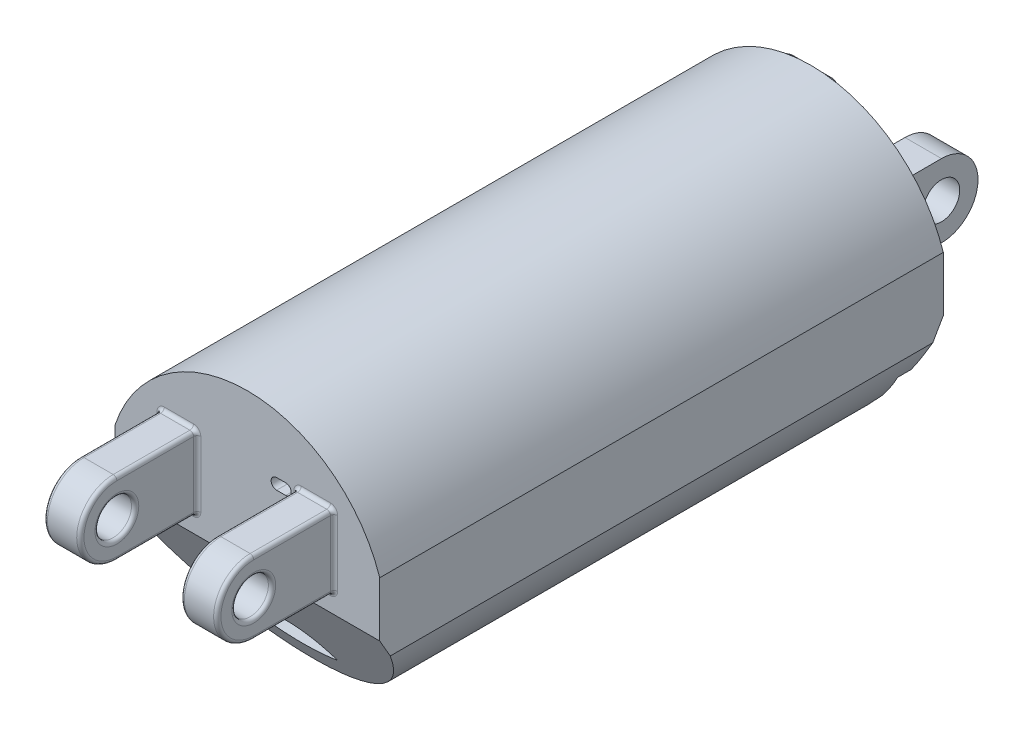
SolidWorks part; units mm, degrees
material "PET"
ref_plane "Front Plane" through (0, 0, 0) normal (0, 0, 1) x (1, 0, 0)
ref_plane "Top Plane" through (0, 0, 0) normal (0, 1, 0) x (1, 0, 0)
ref_plane "Right Plane" through (0, 0, 0) normal (1, 0, 0) x (0, 0, -1)
sketch "Sketch1" plane through (0, 0, 0) normal (0, 0, 1) x (1, 0, 0)
  line L0 (0, 0) -> (0, 5.08)
  line L3 (18.415, 5.08) -> (18.415, 0)
  arc A2 (0, 5.08) -> (18.415, 5.08) centre (9.2075, 2.0562) cw
  arc A3 (0, 0) -> (18.415, 0) centre (9.2075, 3.0238) ccw
  point P7 (9.2075, -6.6675)
  point P8 (9.2075, 11.7475)
  dimension "D1" = 18.415
  dimension "D2" = 18.415
  dimension "D3" = 5.08
extrude "Boss-Extrude1" add sketch "Sketch1" along normal mid plane 39.2112 contours A2 L3 A3 L0
sketch "Sketch2" plane through (0, 0, 0) normal (1, 0, 0) x (0, 0, -1)
  line L4 (15.875, 2.54) -> (-49984.125, 2.54) construction
  line L5 (19.6056, 5.08) -> (19.6056, 0) construction
  line L6 (-19.6056, 5.08) -> (-19.6056, 0) construction
  line L10 (0, -1000) -> (0, 49000) construction
  line L18 (-19.6056, 1.27) -> (-19.6056, -6.6675)
  line L23 (19.6056, -6.6675) -> (15.0229, -6.6675)
  line L24 (19.6056, 1.27) -> (19.6056, -6.6675)
  line L32 (-19.6056, -6.6675) -> (-15.0229, -6.6675)
  line L33 (-19.6056, -6.6675) -> (19.6056, -6.6675) construction
  line L34 (-15.0229, -6.6675) -> (-19.6056, 1.27)
  line L35 (15.0229, -6.6675) -> (19.6056, 1.27)
  line L36 (-19.6056, -6.6675) -> (19.6056, -6.6675) construction
  point P0 (-15.0884, 2.54)
  point P11 (19.6056, 2.54)
  point P14 (-19.6056, 2.54)
  dimension "D2" = 1.27
  dimension "D4" = 60
extrude "Cut-Extrude1" cut sketch "Sketch2" along normal through all
sketch "Sketch3" plane through (0, 0, 19.6056) normal (0, 0, 1) x (1, 0, 0)
  line L1 (9.2075, 11.7475) -> (9.2075, -6.6675) construction
  arc A3 (0, 0) -> (18.415, 0) centre (9.2075, 3.0238) ccw construction
  arc A8 (18.415, 5.08) -> (0, 5.08) centre (9.2075, 2.0562) ccw construction
  arc A9 (6.5303, -4.9606) -> (11.8847, -4.9606) centre (9.2075, -6.6675) cw
  arc A11 (1.2066, 0.3963) -> (17.2084, 0.3963) centre (9.2075, 3.0238) ccw
  arc A12 (6.5303, -4.9606) -> (11.8847, -4.9606) centre (9.2075, 3.0238) ccw
  dimension "D1" = 1.27
  dimension "D2" = 3.175
extrude "Cut-Extrude2" cut sketch "Sketch3" against normal through all contours A12 A9
ref_plane "Plane1" through (14.605, 0, 0) normal (1, 0, 0) x (0, 0, -1)
sketch "Sketch4" plane through (14.605, 0, 0) normal (1, 0, 0) x (0, 0, -1)
  line L0 (-19.6056, 7.62) -> (-22.6536, 7.62)
  line L1 (-19.6056, 7.62) -> (-19.6056, 2.54)
  line L2 (-19.6056, 2.54) -> (-22.6536, 2.54)
  line L3 (-19.6056, 5.08) -> (-19.6056, 1.27) construction
  line L4 (-18.8724, 0) -> (18.8724, 0) construction
  arc A0 (-22.6536, 7.62) -> (-22.6536, 2.54) centre (-22.6536, 5.08) ccw
  circle A1 centre (-22.6536, 5.08) radius 1.27
  dimension "D2" = 2.54
  dimension "D1" = 5.08
  dimension "D3" = 3.048
  dimension "D4" = 2.54
extrude "Boss-Extrude2" add sketch "Sketch4" along normal mid plane 1.27
sketch "Sketch5" plane through (13.97, 0, 0) normal (-1, 0, 0) x (0, 0, 1)
  line L3 (19.6056, 7.62) -> (19.6056, 2.54)
  line L4 (19.6056, 2.54) -> (22.6536, 2.54)
  line L5 (22.6536, 7.62) -> (19.6056, 7.62)
  line L6 (19.6056, 7.62) -> (19.6056, 2.54)
  line L7 (19.6056, 2.54) -> (22.6536, 2.54)
  line L8 (22.6536, 7.62) -> (19.6056, 7.62)
  circle A0 centre (22.6536, 5.08) radius 1.27 construction
  arc A1 (22.6536, 2.54) -> (22.6536, 7.62) centre (22.6536, 5.08) ccw
  arc A2 (22.6536, 2.54) -> (22.6536, 7.62) centre (22.6536, 5.08) ccw
  circle A3 centre (22.6536, 5.08) radius 1.27
  dimension "D1" = 0
extrude "Boss-Extrude3" add sketch "Sketch5" along normal blind 1.27
ref_plane "Plane2" through (9.2075, 0, 0) normal (1, 0, 0) x (0, 0, -1)
mirror "Mirror1" about plane through (9.2075, 0, 0) normal (1, 0, 0) of "Boss-Extrude3", "Boss-Extrude2"
mirror "Mirror2" about plane through (0, 0, 0) normal (0, 0, 1) of "Mirror1", "Boss-Extrude3", "Boss-Extrude2"
sketch "Sketch10" plane through (15.24, 0, 0) normal (1, 0, 0) x (0, 0, -1)
  line L0 (-22.6536, 2.54) -> (-19.6056, 2.54) construction
  line L1 (-19.6056, 7.62) -> (-25.1936, 7.62)
  line L2 (-19.6056, 7.62) -> (-19.6056, 2.54)
  line L3 (-19.6056, 2.54) -> (-25.1936, 2.54)
  line L4 (-19.6056, 2.54) -> (-19.6056, 7.62) construction
  arc A1 (-25.1936, 7.62) -> (-25.1936, 2.54) centre (-25.1936, 5.08) ccw
  circle A2 centre (-25.1936, 5.08) radius 1.27
  arc A3 (-22.6536, 7.62) -> (-22.6536, 2.54) centre (-22.6536, 5.08) ccw construction
  dimension "D1" = 2.54
extrude "Boss-Extrude6" add sketch "Sketch10" against normal up to surface (2.54 mm away) up to face at (12.7, 5.08, 21.7646)
sketch "Sketch12" plane through (3.175, 0, 0) normal (-1, 0, 0) x (0, 0, 1)
  line L0 (22.6536, 2.54) -> (19.6056, 2.54) construction
  line L1 (19.6056, 7.62) -> (25.1936, 7.62)
  line L2 (19.6056, 7.62) -> (19.6056, 2.54)
  line L3 (19.6056, 2.54) -> (25.1936, 2.54)
  line L4 (19.6056, 2.54) -> (19.6056, 7.62) construction
  arc A0 (25.1936, 7.62) -> (25.1936, 2.54) centre (25.1936, 5.08) cw
  arc A1 (25.1936, 2.54) -> (25.1936, 7.62) centre (25.1936, 5.08) ccw construction
extrude "Boss-Extrude7" add sketch "Sketch12" against normal up to surface (2.54 mm away) up to face at (5.715, 5.08, 23.9236)
sketch "Sketch11" plane through (15.24, 0, 0) normal (1, 0, 0) x (0, 0, -1)
  circle A0 centre (-25.1936, 5.08) radius 1.27
  arc A1 (-24.8761, 6.3097) -> (-24.8761, 3.8503) centre (-22.6536, 5.08) ccw construction
extrude "Cut-Extrude5" cut sketch "Sketch11" against normal up to surface (12.065 mm away) up to face at (3.175, 5.08, 23.0346)
sketch "Sketch16" plane through (0, 0, 19.6056) normal (0, 0, 1) x (1, 0, 0)
  line L0 (18.415, 1.27) -> (0, 1.27) construction
  line L1 (6.5405, 1.8415) -> (11.8745, 1.8415) construction
  line L2 (6.5405, 1.8415) -> (6.5405, 7.5311) construction
  line L3 (6.5405, 7.5311) -> (11.8745, 7.5311) construction
  line L4 (11.8745, 1.8415) -> (11.8745, 7.5311) construction
  line L5 (6.5405, 1.8415) -> (11.8745, 7.5311) construction
  line L6 (6.5405, 7.5311) -> (11.8745, 1.8415) construction
  line L7 (2.034, -3.4925) -> (16.381, -3.4925) construction
  line L8 (11.2395, 7.1501) -> (11.8745, 7.1501) construction
  line L9 (11.2395, 7.5311) -> (11.8745, 7.5311)
  line L10 (11.2395, 6.7691) -> (11.8745, 6.7691)
  arc A0 (11.8847, -4.9606) -> (6.5303, -4.9606) centre (9.2075, -6.6675) ccw construction
  arc A1 (0, 0) -> (18.415, 0) centre (9.2075, 3.0238) ccw construction
  arc A2 (11.2395, 7.5311) -> (11.2395, 6.7691) centre (11.2395, 7.1501) ccw
  arc A3 (11.8745, 6.7691) -> (11.8745, 7.5311) centre (11.8745, 7.1501) ccw
  point P0 (9.2075, 4.6863)
  point P8 (9.2075, 1.27)
  point P13 (11.557, 7.1501)
  dimension "D1" = 5.334
  dimension "D2" = 5.6896
  dimension "D3" = 5.334
  dimension "D4" = 0.635
  dimension "D5" = 0.762
extrude "Cut-Extrude7" cut sketch "Sketch16" against normal blind 13.97
sketch "Sketch17" plane through (0, 0, -19.6056) normal (0, 0, -1) x (-1, 0, 0)
  line L0 (-16.381, -3.4925) -> (-2.034, -3.4925) construction
  line L1 (-11.8745, 1.8415) -> (-6.5405, 1.8415) construction
  line L2 (-11.8745, 1.8415) -> (-11.8745, 7.5311) construction
  line L3 (-11.8745, 7.5311) -> (-6.5405, 7.5311) construction
  line L4 (-6.5405, 1.8415) -> (-6.5405, 7.5311) construction
  line L5 (-11.8745, 1.8415) -> (-6.5405, 7.5311) construction
  line L6 (-11.8745, 7.5311) -> (-6.5405, 1.8415) construction
  line L7 (-7.5565, 7.1501) -> (-6.9215, 7.1501) construction
  line L8 (-7.5565, 7.5311) -> (-6.9215, 7.5311)
  line L9 (-7.5565, 6.7691) -> (-6.9215, 6.7691)
  arc A0 (-18.415, 0) -> (0, 0) centre (-9.2075, 3.0238) ccw construction
  arc A1 (-6.5303, -4.9606) -> (-11.8847, -4.9606) centre (-9.2075, -6.6675) ccw construction
  arc A2 (-7.5565, 7.5311) -> (-7.5565, 6.7691) centre (-7.5565, 7.1501) ccw
  arc A3 (-6.9215, 6.7691) -> (-6.9215, 7.5311) centre (-6.9215, 7.1501) ccw
  point P0 (-9.2075, 4.6863)
  point P10 (-7.239, 7.1501)
  point P16 (-9.2075, -3.4925)
  dimension "D1" = 5.334
  dimension "D2" = 5.6896
  dimension "D3" = 5.334
  dimension "D4" = 0.762
  dimension "D5" = 0.635
extrude "Cut-Extrude8" cut sketch "Sketch17" against normal blind 16.51
fillet "Fillet1" radius 0.254 24 edges at (3.175, 5.08, 27.7336) (3.175, 5.08, 19.6056) (3.175, 5.08, 26.4636) (3.175, 2.54, 22.3996) (4.445, 2.54, 19.6056) (5.715, 5.08, 19.6056) (5.715, 2.54, 22.3996) (5.715, 5.08, 27.7336) (5.715, 5.08, 23.9236) (4.445, 7.62, 19.6056) (5.715, 7.62, 22.3996) (3.175, 7.62, 22.3996) (13.97, 2.54, 19.6056) (13.97, 7.62, 19.6056) (12.7, 2.54, 22.3996) (12.7, 5.08, 19.6056) (12.7, 7.62, 22.3996) (12.7, 5.08, 27.7336) (12.7, 5.08, 26.4636) (15.24, 5.08, 19.6056) (15.24, 2.54, 22.3996) (15.24, 5.08, 27.7336) (15.24, 7.62, 22.3996) (15.24, 5.08, 23.9236)
sketch "Sketch18" plane through (0, 0, -19.6056) normal (0, 0, -1) x (-1, 0, 0)
  line L0 (-18.415, 5.08) -> (-18.415, 1.27) construction
  line L1 (-17.78, 5.08) -> (-15.875, 5.08)
  line L2 (-17.78, 5.08) -> (-17.78, -6.6675)
  line L3 (-17.78, -6.6675) -> (-15.875, -6.6675)
  line L4 (-15.875, 5.08) -> (-15.875, -6.6675)
  line L5 (-0.635, 5.08) -> (-2.54, 5.08)
  line L6 (-0.635, 5.08) -> (-0.635, -6.6675)
  line L7 (-0.635, -6.6675) -> (-2.54, -6.6675)
  line L8 (-2.54, 5.08) -> (-2.54, -6.6675)
  line L9 (-18.415, 5.08) -> (0, 5.08) construction
  line L10 (0, 1.27) -> (0, 5.08) construction
  arc A0 (-18.415, 0) -> (0, 0) centre (-9.2075, 3.0238) ccw construction
  dimension "D1" = 1.905
  dimension "D2" = 0.635
  dimension "D3" = 0.635
extrude "Cut-Extrude9" cut sketch "Sketch18" against normal blind 2.54
sketch "Sketch19" plane through (0, 0, 0) normal (-1, 0, 0) x (0, 0, 1)
  text T0 "Mid 3\r\n"
extrude "Cut-Extrude10" cut sketch "Sketch19" against normal blind 1
equation "\"D1@Sketch1\"=0.725"
equation "\"D2@Sketch1\"=0.725"
equation "\"D1@Boss-Extrude1\"=2.375*.65"
